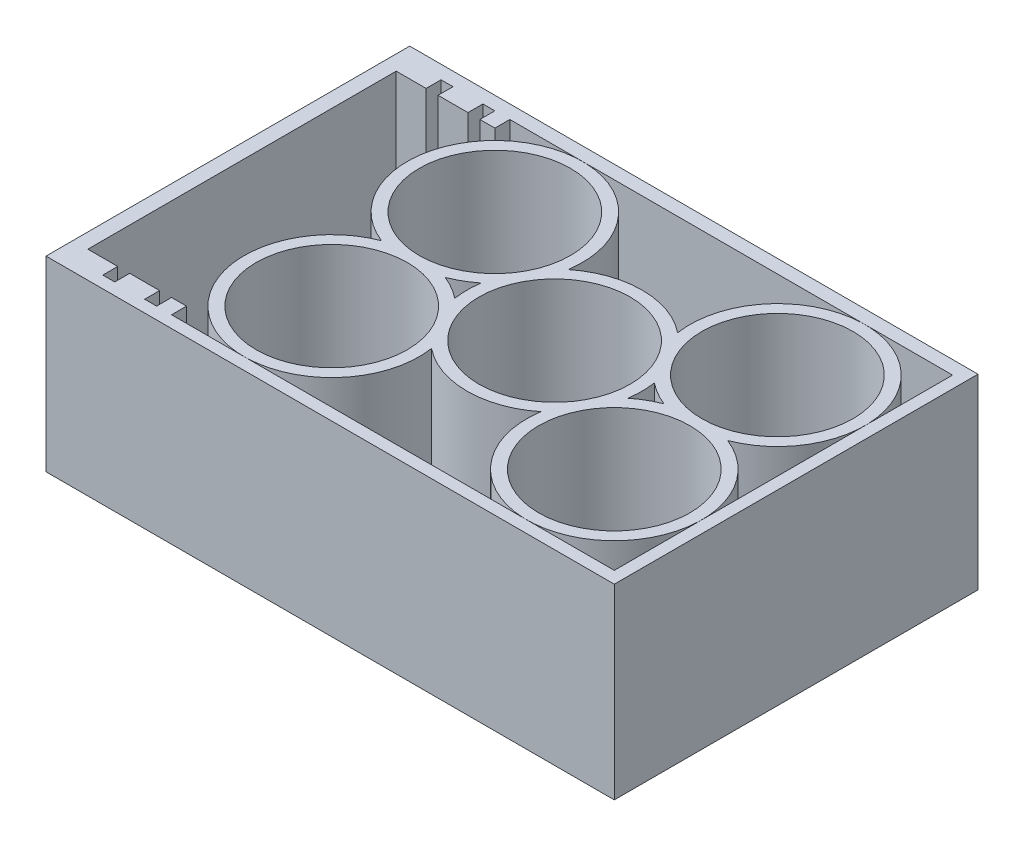
SolidWorks part; units mm, degrees
ref_plane "Front Plane" through (0, 0, 0) normal (0, 0, 1) x (1, 0, 0)
ref_plane "Top Plane" through (0, 0, 0) normal (0, 1, 0) x (1, 0, 0)
ref_plane "Right Plane" through (0, 0, 0) normal (1, 0, 0) x (0, 0, -1)
sketch "Sketch1" plane through (0, 0, 0) normal (0, 1, 0) x (1, 0, 0)
  line L0 (22.3334, 17.5114) -> (22.3334, 7.3964)
  line L1 (22.3334, 29.2264) -> (3.428, 18.3114)
  line L2 (3.428, 18.3114) -> (-15.4773, 29.2264)
  line L3 (-15.4773, 17.5114) -> (-15.4773, 7.3964)
  line L4 (34.0484, 40.9414) -> (34.0484, -4.3186)
  line L5 (-27.1923, 7.3964) -> (-27.1923, 18.3114)
  line L6 (-27.1923, 18.3114) -> (34.0484, 18.3114)
  line L7 (-27.1923, 40.9414) -> (-28.7923, 40.9414)
  line L9 (-27.1923, 40.9414) -> (-27.1923, -4.3186)
  line L11 (-28.7923, 40.9414) -> (-28.7923, -4.3186)
  line L12 (-28.7923, -4.3186) -> (-27.1923, -4.3186)
  line L13 (-27.1923, 38.9414) -> (-25.1923, 38.9414)
  line L14 (-32.7923, 40.9414) -> (-32.7923, -4.3186)
  line L15 (-25.1923, 38.9414) -> (-25.1923, 40.9414)
  line L16 (-34.3923, 40.9414) -> (-32.7923, 40.9414)
  line L18 (-34.3923, 40.9414) -> (-34.3923, -4.3186)
  line L22 (-34.3923, -4.3186) -> (-32.7923, -4.3186)
  line L23 (-25.1923, 40.9414) -> (34.0484, 40.9414)
  line L24 (-38.3923, 38.9414) -> (-38.3923, -2.3186)
  line L25 (-27.1923, -2.3186) -> (-25.1923, -2.3186)
  line L29 (-34.3923, 40.9414) -> (-34.3923, 38.9414)
  line L32 (-34.3923, 38.9414) -> (-38.3923, 38.9414)
  line L36 (-32.7923, 38.9414) -> (-28.7923, 38.9414)
  line L40 (-34.3923, -4.3186) -> (-34.3923, -2.3186)
  line L41 (-34.3923, -2.3186) -> (-38.3923, -2.3186)
  line L42 (-32.7923, -2.3186) -> (-28.7923, -2.3186)
  line L43 (-25.1923, -2.3186) -> (-25.1923, -4.3186)
  line L44 (-25.1923, -4.3186) -> (34.0484, -4.3186)
  line L45 (-34.3923, 38.9414) -> (-38.3923, 38.9414)
  line L46 (-32.7923, 40.9414) -> (-34.3923, 40.9414)
  line L47 (-32.7923, 40.9414) -> (-32.7923, -4.3186)
  line L48 (-32.7923, -4.3186) -> (-34.3923, -4.3186)
  line L49 (-34.3923, 40.9414) -> (-34.3923, -4.3186)
  line L50 (-38.3923, -2.3186) -> (-34.9331, -2.3186)
  line L51 (-25.1923, 38.9414) -> (-27.1923, 38.9414)
  line L52 (-28.7923, 38.9414) -> (-32.7923, 38.9414)
  line L53 (-34.3923, 38.9414) -> (-38.3923, 38.9414)
  line L54 (-38.3923, -2.3186) -> (-34.3923, -2.3186)
  line L55 (-32.7923, -2.3186) -> (-28.7923, -2.3186)
  line L56 (-27.1923, -2.3186) -> (-25.1923, -2.3186)
  line L57 (-25.1923, -2.3186) -> (-25.1923, -4.3186)
  line L58 (34.0484, -4.3186) -> (-25.1923, -4.3186)
  line L59 (34.0484, 40.9414) -> (34.0484, -4.3186)
  line L61 (35.6484, -5.9186) -> (-40.3923, -5.9186)
  line L62 (35.6484, -5.9186) -> (35.6484, 42.7484)
  line L63 (35.6484, 42.7484) -> (-40.3923, 42.7484)
  line L64 (-40.3923, -5.9186) -> (-40.3923, 42.7484)
  line L65 (34.0484, -4.3186) -> (-38.3923, -4.3186)
  line L66 (34.0484, -4.3186) -> (34.0484, 40.9414)
  line L67 (34.0484, 40.9414) -> (-38.3923, 40.9414)
  line L68 (-38.3923, -4.3186) -> (-38.3923, 40.9414)
  line L69 (-40.3923, 42.7484) -> (35.6484, 42.7484)
  line L70 (-40.3923, 42.7484) -> (-40.3923, -5.9186)
  line L71 (-40.3923, -5.9186) -> (35.6484, -5.9186)
  line L72 (35.6484, 42.7484) -> (35.6484, -5.9186)
  circle A0 centre (22.3334, 29.2264) radius 10.115
  circle A1 centre (22.3334, 29.2264) radius 11.715
  circle A2 centre (22.3334, 7.3964) radius 10.115
  circle A3 centre (22.3334, 7.3964) radius 11.715
  circle A4 centre (3.428, 18.3114) radius 10.115
  circle A5 centre (3.428, 18.3114) radius 11.715
  circle A6 centre (-15.4773, 29.2264) radius 11.715
  circle A7 centre (-15.4773, 29.2264) radius 10.115
  circle A8 centre (-15.4773, 7.3964) radius 10.115
  circle A9 centre (-15.4773, 7.3964) radius 11.715
extrude "Boss-Extrude4" add sketch "Sketch1" along normal blind 25 contours L64 L61 L62 L63 L65 L68 L24 L67 L16 L7 L23 L4 L66 L44 L12 L22 | L68 L65 L18 L41 | L68 L32 L18 L67 | A9 A7 A5 A6 | A9 A5 A8 A6 | A6 L6 | L6 A9 | A9 A6 A5 A7 | A5 A9 A6 A8 | A5 A6 L2 | L2 A6 A5 | A6 A4 A1 A5 | A6 A5 L6 A4 | A9 A4 L6 A5 | A5 A9 | A9 A5 A3 A4 | A5 A0 A3 A1 | L1 A5 A1 | A1 A5 L1 | A5 A1 A3 A0 | L6 A5 A1 A4 | A3 A5 L6 A4 | A3 A5 | L6 A3 | A1 L6 | A5 A2 A1 A3 | A5 A3 A1 A2 | L15 L67 L9 L13 | L11 L67 L14 L36 | L65 L11 L42 L14 | L65 L43 L25 L9 | A6 | A4 region at (13.6822, 0, -22.3806) region at (12.5636, 0, -26.1549) region at (17.0188, 0, -20.0213) region at (12.0791, 0, -25.1572) region at (3.428, 0, -28.6138) region at (14.0571, 0, -19.8388) region at (22.3334, 0, -18.6324) region at (14.0571, 0, -16.784) region at (-6.8262, 0, -22.3806) region at (-7.2011, 0, -19.8388) region at (-5.2231, 0, -25.1572) region at (22.3334, 0, -17.9905) region at (31.7362, 0, -13.823) region at (17.0188, 0, -16.6015) region at (-5.7076, 0, -26.1549) region at (-7.2011, 0, -16.784) region at (12.8807, 0, -12.8539) region at (11.1034, 0, -11.3404) region at (-10.1628, 0, -20.0213) region at (-6.0247, 0, -12.8539) region at (-15.4773, 0, -18.6324) region at (-15.4773, 0, -17.9905) region at (-10.1628, 0, -16.6015) region at (-26.1923, 0, -39.9414) region at (-4.1209, 0, -8.2606) region at (-26.1923, 0, 3.3186) region at (-30.7923, 0, -39.9414) region at (-30.7923, 0, 3.3186) region at (-36.3923, 0, -39.9414) region at (-36.3923, 0, 3.3186) region at (-2.372, 0, 5.0158)
extrude "Cut-Extrude1" cut sketch "Sketch1<9>" along normal blind 36 contours L6 A4 L1 | L1 A4 L2 | L2 A4 L6 | A4 L6 | A7 region at (9.8674, 0, -20.0368) region at (3.428, 0, -23.8881) region at (-3.0114, 0, -20.0368) region at (3.428, 0, -14.0185) region at (-10.5629, 0, -20.7143)
sketch "Sketch1<9>" plane through (0, 0, 0) normal (0, 1, 0) x (1, 0, 0) same geometry as "Sketch1"
sketch "Sketch3" plane through (0, 0, 0) normal (0, -1, 0) x (1, 0, 0)
  line L1 (-40.3923, 5.9186) -> (35.6484, 5.9186)
  line L2 (-40.3923, 5.9186) -> (-40.3923, -42.7484)
  line L3 (-40.3923, -42.7484) -> (35.6484, -42.7484)
  line L4 (35.6484, 5.9186) -> (35.6484, -42.7484)
